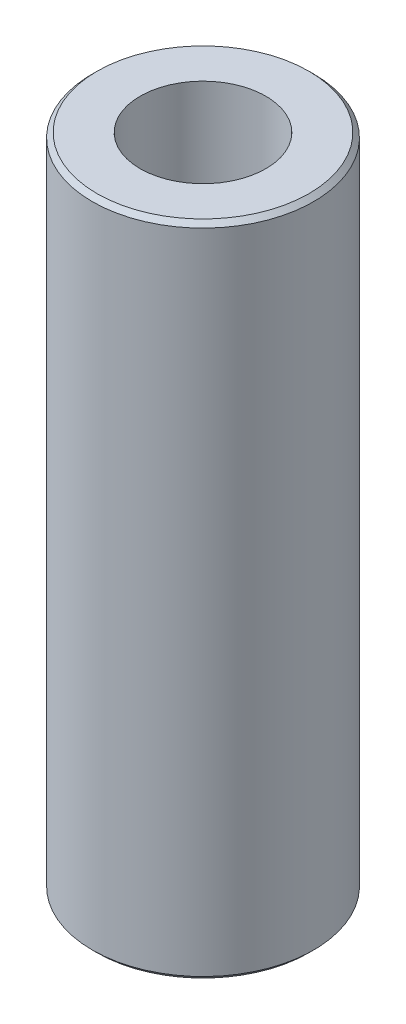
SolidWorks part; units mm, degrees
ref_plane "Front Plane" through (0, 0, 0) normal (0, 0, 1) x (1, 0, 0)
ref_plane "Top Plane" through (0, 0, 0) normal (0, 1, 0) x (1, 0, 0)
ref_plane "Right Plane" through (0, 0, 0) normal (1, 0, 0) x (0, 0, -1)
sketch "Sketch1" plane through (0, 0, 0) normal (0, 1, 0) x (1, 0, 0)
  circle A0 centre (0, 0) radius 32.5
  dimension "SHAFT_OD" = 65
extrude "Boss-Extrude1" add sketch "Sketch1" along normal blind 193.1085
sketch "Sketch2" plane through (0, 0, 0) normal (0, 1, 0) x (1, 0, 0)
  circle A0 centre (0, 0) radius 18.4602
  dimension "BORE_D" = 36.9205
extrude "Cut-Extrude1" cut sketch "Sketch2" along normal through all
chamfer "Chamfer1" distance 1.3657 angle 45 2 edges at (0, 193.1085, 32.5) (0, 0, 32.5)
